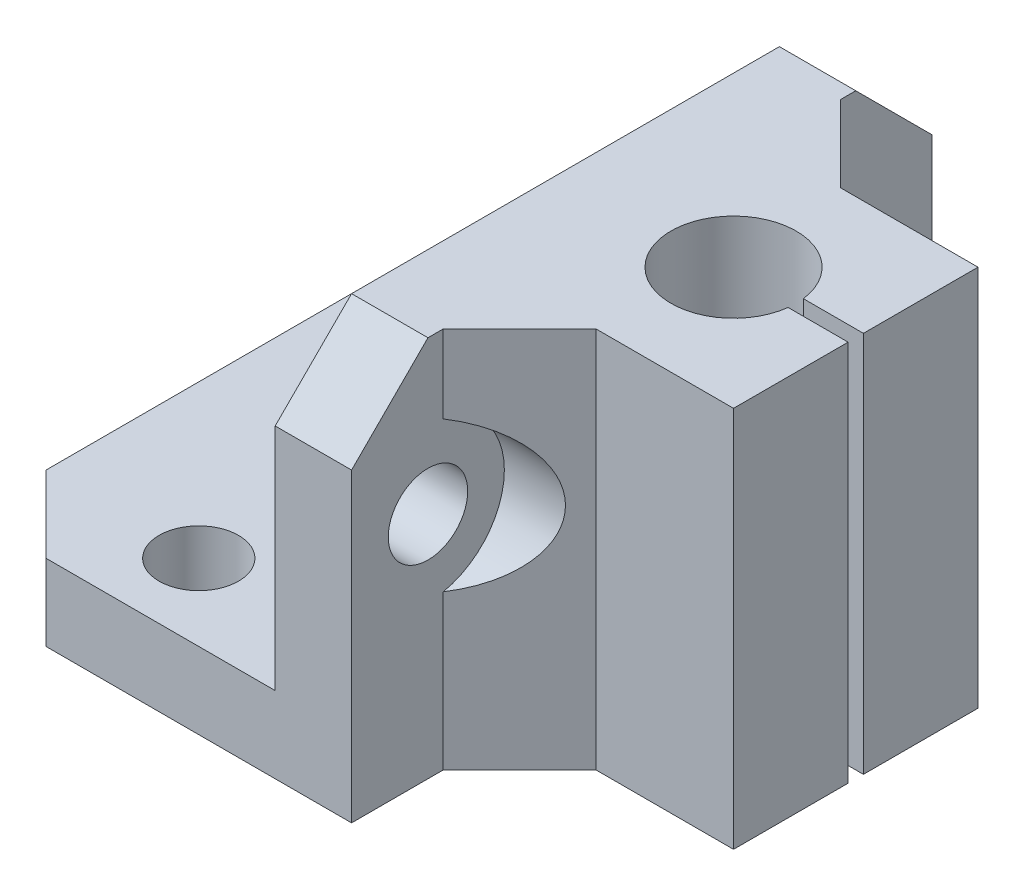
SolidWorks part; units mm, degrees
ref_plane "Front Plane" through (0, 0, 0) normal (0, 0, 1) x (1, 0, 0)
ref_plane "Top Plane" through (0, 0, 0) normal (0, 1, 0) x (1, 0, 0)
ref_plane "Right Plane" through (0, 0, 0) normal (1, 0, 0) x (0, 0, -1)
sketch "Sketch1" plane through (0, 0, 0) normal (0, 1, 0) x (1, 0, 0)
  line L0 (10, 0) -> (10, -38) construction
  line L1 (0, 0) -> (20, 0)
  line L2 (0, 0) -> (0, -38)
  line L3 (0, -38) -> (20, -38)
  line L4 (20, 0) -> (20, -38)
  line L5 (20, 0) -> (25, 0)
  line L6 (20, 0) -> (20, -38)
  line L7 (20, -38) -> (25, -38)
  line L8 (25, 0) -> (25, -38)
  line L9 (25, -11) -> (39, -11)
  line L10 (25, -11) -> (25, -27)
  line L11 (25, -27) -> (39, -27)
  line L12 (39, -11) -> (39, -27)
  line L13 (25, -19) -> (39, -19) construction
  line L14 (35.0694, -18.5) -> (39, -18.5)
  line L15 (35.0694, -19.5) -> (39, -19.5)
  line L16 (37.8747, -18.5) -> (37.8747, -19.5) construction
  line L17 (37.8747, -19) -> (38.7387, -19) construction
  circle A0 centre (10, -5) radius 2.6
  circle A1 centre (10, -33) radius 2.6
  circle A2 centre (31, -19) radius 4.1
  dimension "D8" = 5.2
  dimension "D9" = 5.2
  dimension "D10" = 8.2
  dimension "D1" = 20
  dimension "D2" = 38
  dimension "D3" = 5
  dimension "D4" = 16
  dimension "D5" = 14
  dimension "D6" = 11
  dimension "D7" = 11
  dimension "D11" = 6
  dimension "D12" = 8
  dimension "D13" = 1
  dimension "D14" = 5
  dimension "D15" = 5
extrude "Boss-Extrude1" add sketch "Sketch1" along normal blind 5 contours L4 L1 L2 L3 A1 A0 region at (10, 0, 19)
extrude "Boss-Extrude2" add sketch "Sketch1<4>" along normal blind 25 contours L8 L5 L4 L7 | A2 L14 L12 L9 L8 L11 L15 region at (22.5, 0, 19) region at (32, 0, 11.2126)
sketch "Sketch1<4>" plane through (0, 0, 0) normal (0, 1, 0) x (1, 0, 0) same geometry as "Sketch1"
chamfer "Chamfer1" distance 5 angle 45 2 edges at (25, 12.5, 11) (25, 12.5, 27)
sketch "Sketch2" plane through (20, 0, 0) normal (-1, 0, 0) x (0, 0, 1)
  line L0 (0, 15) -> (38, 15) construction
  line L1 (0, 25) -> (0, 5) construction
  line L2 (38, 25) -> (38, 5) construction
  circle A0 centre (5, 15) radius 2.6
  circle A1 centre (33, 15) radius 2.6
  dimension "D1" = 5.2
  dimension "D2" = 5.2
  dimension "D3" = 5
  dimension "D4" = 5
extrude "Cut-Extrude1" cut sketch "Sketch2" against normal through all
ref_plane "Plane1" through (25, 0, 0) normal (-1, 0, 0) x (0, 0, 1)
sketch "Sketch3" plane through (25, 0, 0) normal (-1, 0, 0) x (0, 0, 1)
  circle A0 centre (5, 15) radius 5
  circle A1 centre (33, 15) radius 5
  dimension "D1" = 10
  dimension "D2" = 10
extrude "Cut-Extrude2" cut sketch "Sketch3" against normal through all
chamfer "Chamfer2" distance 5 angle 45 2 edges at (22.5, 25, 0) (22.5, 25, 38)
chamfer "Chamfer3" distance 5 angle 45 2 edges at (0, 2.5, 0) (0, 2.5, 38)
